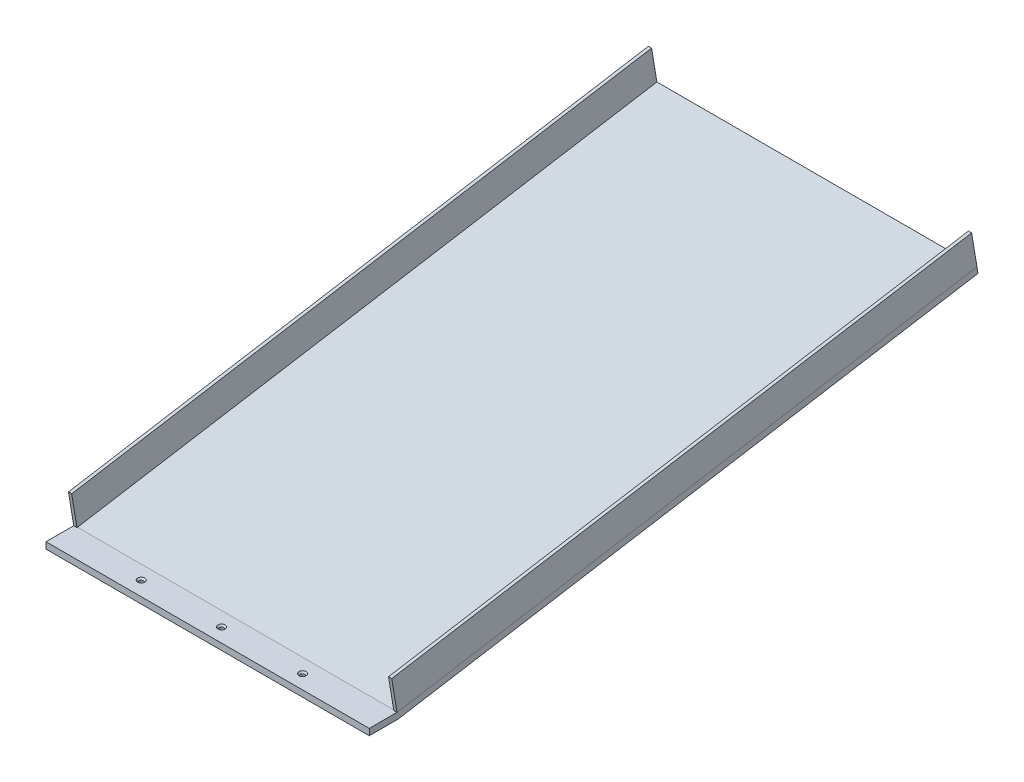
SolidWorks part; units mm, degrees
ref_plane "Front Plane" through (0, 0, 0) normal (0, 0, 1) x (1, 0, 0)
ref_plane "Top Plane" through (0, 0, 0) normal (0, 1, 0) x (1, 0, 0)
ref_plane "Right Plane" through (0, 0, 0) normal (1, 0, 0) x (0, 0, -1)
sketch "Sketch1" plane through (0, 0, 0) normal (0, 1, 0) x (1, 0, 0)
  line L0 (-128.27, 0) -> (128.27, 0)
  point P4 (0, 0)
  dimension "D1" = 256.54
ref_plane "Plane2" through (0, 76.2, 0) normal (0, 1, 0) x (1, 0, 0)
sketch "Sketch2" plane through (0, 76.2, 0) normal (0, 1, 0) x (1, 0, 0)
  line L0 (-128.27, 460.248) -> (128.27, 460.248)
  line L1 (-128.27, 0) -> (128.27, 0) construction
  point P2 (0, 460.248)
  dimension "D1" = 460.248
ref_plane "Plane3" through (0, 0, 0) normal (0, 0.9866, 0.1633) x (1, 0, 0)
sketch "Sketch3" plane through (0, 0, 0) normal (0, 0.9866, 0.1633) x (1, 0, 0)
  line L0 (-128.27, 466.5133) -> (-128.27, 0)
  line L1 (-128.27, 0) -> (128.27, 0)
  line L2 (128.27, 0) -> (128.27, 466.5133)
  line L3 (128.27, 466.5133) -> (-128.27, 466.5133)
extrude "Boss-Extrude1" add sketch "Sketch3" along normal blind 5.08
ref_plane "Plane4" through (128.27, 0, 0) normal (1, 0, 0) x (0, 0, -1)
sketch "Sketch4" plane through (128.27, 0, 0) normal (1, 0, 0) x (0, 0, -1)
  line L0 (-0.8298, 5.0118) -> (459.4182, 81.2118)
  line L1 (459.4182, 81.2118) -> (455.2129, 106.6118)
  line L2 (455.2129, 106.6118) -> (-5.0351, 30.4118)
  line L3 (-5.0351, 30.4118) -> (-0.8298, 5.0118)
  dimension "D1" = 25.4
extrude "Boss-Extrude2" add sketch "Sketch4" against normal blind 2.54 separate body
ref_plane "Plane5" through (-128.27, 0, 0) normal (-1, 0, 0) x (0, 0, 1)
sketch "Sketch5" plane through (-128.27, 0, 0) normal (-1, 0, 0) x (0, 0, 1)
  line L0 (-459.4182, 81.2118) -> (-455.2129, 106.6118)
  line L1 (-455.2129, 106.6118) -> (5.0351, 30.4118)
  line L2 (5.0351, 30.4118) -> (0.8298, 5.0118)
  line L3 (0.8298, 5.0118) -> (-459.4182, 81.2118)
extrude "Boss-Extrude3" add sketch "Sketch5" against normal blind 2.54
sketch "Sketch7" plane through (0, 0, 0) normal (0, 1, 0) x (1, 0, 0)
  line L0 (128.27, -44.6665) -> (128.27, 44.6665) construction
  line L1 (-128.27, 0) -> (128.27, 0)
  line L2 (-128.27, 0) -> (-128.27, -22.86)
  line L3 (-128.27, -22.86) -> (128.27, -22.86)
  line L4 (128.27, 0) -> (128.27, -22.86)
  dimension "D1" = 22.86
extrude "Boss-Extrude5" add sketch "Sketch7" along normal blind 5.08
sketch "Sketch8" plane through (0, 5.08, 0) normal (0, 1, 0) x (1, 0, 0)
  line L0 (-128.27, -11.8505) -> (128.27, -11.6388) construction
  line L1 (-128.27, -0.8411) -> (-128.27, -22.86) construction
  line L2 (128.27, -22.86) -> (128.27, -0.4177) construction
  line L3 (0, 0) -> (0, -22.86) construction
  line L4 (-128.27, -22.86) -> (128.27, -22.86) construction
  line L5 (-64.135, 0) -> (-64.135, -22.86) construction
  line L6 (-128.27, 0) -> (128.27, 0) construction
  line L7 (64.135, 0) -> (64.135, -22.86) construction
  dimension "D1" = 64.135
  dimension "D2" = 64.135
hole_wizard "CSK for #4 Flat Head Machine Screw1" positions "Sketch9" profile "Sketch10" countersink size "#4" standard "ANSI Inch" end condition through all
sketch "Sketch9" plane through (0, 5.08, 0) normal (0, 1, 0) x (1, 0, 0)
  line L0 (-64.135, 0) -> (-64.135, -22.86) construction
  line L1 (-128.27, -11.8505) -> (128.27, -11.6388) construction
  point P0 (-64.135, -11.43)
  point P4 (0, -11.7447)
  point P8 (64.2268, -11.6917)
sketch "Sketch10" plane through (-64.135, 5.08, 11.43) normal (1, 0, 0) x (0, 0, 1)
  line L0 (0, 0) -> (0, 5.08)
  line L1 (0, 5.08) -> (1.7272, 5.08)
  line L2 (1.7272, 5.08) -> (1.7272, 1.3003)
  line L3 (1.7272, 1.3003) -> (2.8575, 0)
  line L5 (2.8575, 0) -> (0, 0)
  line L6 (-1.7272, 1.3003) -> (-2.8575, 0) construction
  line L11 (0, -6.35) -> (0, 107.95) construction
  dimension "Thru Hole Dia." = 3.4544
  dimension "Thru Hole Depth" = 5.08
  dimension "Near C'Sink Dia." = 5.715
  dimension "Near C'Sink Angle" = 82
